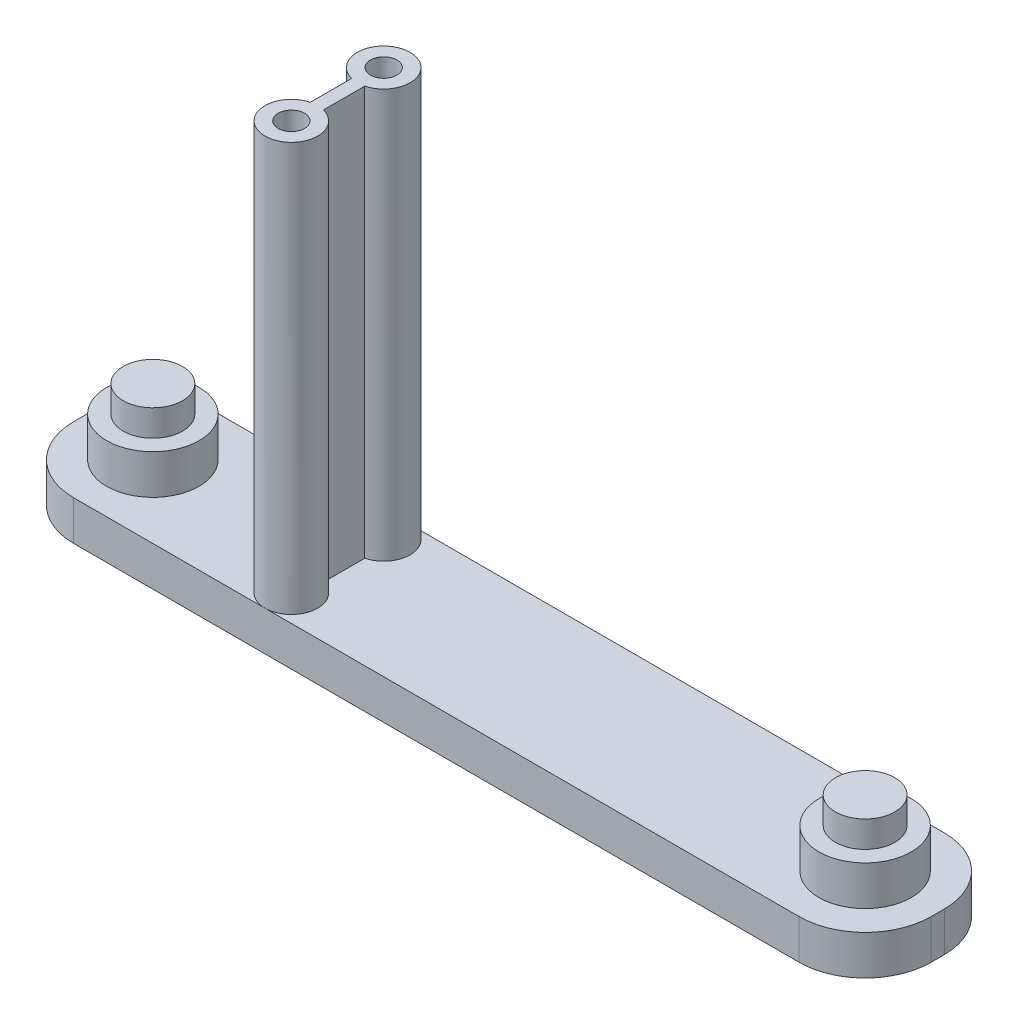
SolidWorks part; units mm, degrees
material "ABS"
ref_plane "Front Plane" through (0, 0, 0) normal (0, 0, 1) x (1, 0, 0)
ref_plane "Top Plane" through (0, 0, 0) normal (0, 1, 0) x (1, 0, 0)
ref_plane "Right Plane" through (0, 0, 0) normal (1, 0, 0) x (0, 0, -1)
sketch "Sketch2" plane through (0, 0, 0) normal (0, 1, 0) x (1, 0, 0)
  line L0 (-56.4145, 13.5709) -> (8.5855, 13.5709) construction
  line L1 (-56.4145, 19.0709) -> (8.5855, 19.0709)
  line L2 (-56.4145, 19.0709) -> (-56.4145, 8.0709)
  line L3 (-56.4145, 8.0709) -> (8.5855, 8.0709)
  line L4 (8.5855, 19.0709) -> (8.5855, 8.0709)
  line L5 (-23.9145, 19.0709) -> (-23.9145, 8.0709) construction
  line L6 (-36.9145, 19.0709) -> (-36.9145, 8.0709) construction
  line L7 (-37.4145, 15.1344) -> (-37.4145, 12.0074)
  line L8 (-36.4145, 15.1344) -> (-36.4145, 12.0074)
  line L9 (-37.4145, 15.1344) -> (-36.4145, 15.1344) construction
  circle A0 centre (-50.9145, 13.5709) radius 3.5
  circle A1 centre (3.0855, 13.5709) radius 3.5
  circle A2 centre (-50.9145, 13.5709) radius 2.25
  circle A3 centre (3.0855, 13.5709) radius 2.25
  circle A4 centre (-36.9145, 17.0709) radius 2
  circle A5 centre (-36.9145, 10.0709) radius 2
  dimension "D3" = 7
  dimension "D4" = 4.5
  dimension "D6" = 1
  dimension "D1" = 65
  dimension "D2" = 11
  dimension "D5" = 13
  dimension "D7" = 54
  dimension "D8" = 7
extrude "Boss-Extrude1" add sketch "Sketch2" against normal blind 3 contours A0 | A1 | L4 L1 L2 L3 A0 A1 | A2 | A3 | A4 | A5 | L3 A5 A4 L1 L2 A0 | A5 A4 region at (-46.4345, 0, -13.5709) region at (-14.9558, 0, -13.5709) region at (-36.9145, 0, -17.0709) region at (-36.9145, 0, -13.5709) region at (-36.9145, 0, -10.0709) region at (-54.3155, 0, -13.5709) region at (-0.3155, 0, -13.5709) region at (-50.9145, 0, -13.5709) region at (3.0855, 0, -13.5709)
extrude "Boss-Extrude2" add sketch "Sketch2<4>" along normal blind 3 contours A0 | A1 | A2 | A3 region at (-54.3155, 0, -13.5709) region at (-0.3155, 0, -13.5709) region at (-50.9145, 0, -13.5709) region at (3.0855, 0, -13.5709)
sketch "Sketch2<4>" plane through (0, 0, 0) normal (0, 1, 0) x (1, 0, 0) same geometry as "Sketch2"
extrude "Boss-Extrude3" add sketch "Sketch2<5>" along normal offset from surface (5 mm away) 2 contours A2 | A3 region at (-50.9145, 0, -13.5709) region at (3.0855, 0, -13.5709) up to face at (-50.9145, 3, -10.0709) offset beyond the face yes
sketch "Sketch2<5>" plane through (0, 0, 0) normal (0, 1, 0) x (1, 0, 0) same geometry as "Sketch2"
extrude "Boss-Extrude4" add sketch "Sketch2<6>" along normal offset from surface (31 mm away) 31 contours A4 | A5 | L7 A5 L8 A4 region at (-36.9145, 0, -17.0709) region at (-36.9145, 0, -13.5709) region at (-36.9145, 0, -10.0709) up to face at (3.0855, 0, -10.0709) offset beyond the face yes
sketch "Sketch2<6>" plane through (0, 0, 0) normal (0, 1, 0) x (1, 0, 0) same geometry as "Sketch2"
sketch "Sketch3" plane through (0, 31, 0) normal (0, 1, 0) x (1, 0, 0)
  circle A0 centre (-36.9145, 17.0709) radius 2 construction
  circle A1 centre (-36.9145, 17.0709) radius 2 construction
  circle A2 centre (-36.9145, 10.0709) radius 2 construction
  circle A3 centre (-36.9145, 10.0709) radius 2 construction
  circle A4 centre (-36.9145, 10.0709) radius 1
  circle A5 centre (-36.9145, 17.0709) radius 1
  dimension "D1" = 2
fillet "Fillet1" radius 5 4 edges at (8.5855, -1.5, -19.0709) (8.5855, -1.5, -8.0709) (-56.4145, -1.5, -19.0709) (-56.4145, -1.5, -8.0709)
extrude "Cut-Extrude1" cut sketch "Sketch3" against normal blind 10
